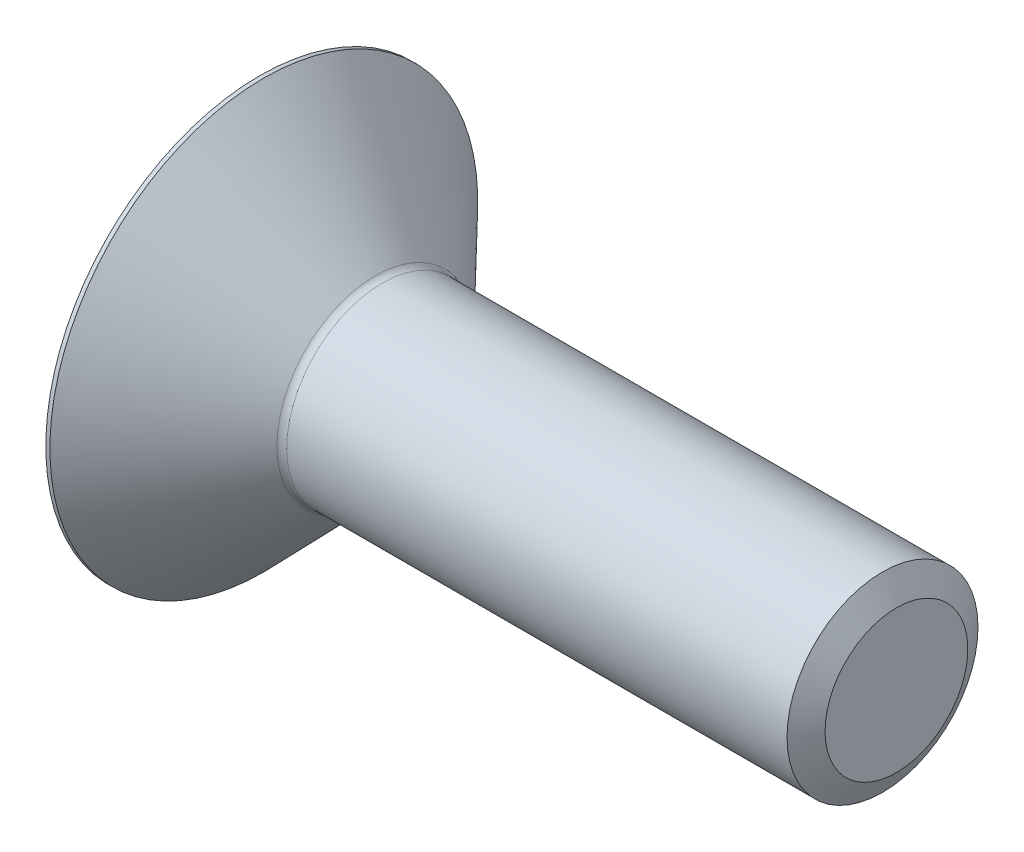
SolidWorks part; units mm, degrees
ref_plane "前视基准面" through (0, 0, 0) normal (0, 0, 1) x (1, 0, 0)
ref_plane "上视基准面" through (0, 0, 0) normal (0, 1, 0) x (1, 0, 0)
ref_plane "右视基准面" through (0, 0, 0) normal (1, 0, 0) x (0, 0, -1)
sketch "尺寸草图" plane through (0, 0, 0) normal (0, 0, 1) x (1, 0, 0)
  line L0 (0, 0) -> (40, 0) construction
  line L1 (40, 0) -> (40, 6) construction
  line L2 (40, 6) -> (38.25, 6) construction
  line L3 (38.25, 6) -> (8, 6) construction
  line L4 (0, 13.44) -> (7.44, 13.44) construction
  line L5 (7.44, 13.44) -> (8.04, 13.44) construction
  point P3 (40, 6.75)
  point P7 (0, 13.44)
  point P8 (0, 6)
  point P9 (0, 9.15)
  point P13 (0, 4)
  point P15 (4.3, 13.44)
  point P16 (6.24, 13.44)
  dimension "l" = 40
  dimension "d" = 12
  dimension "P" = 1.75
  dimension "b" = 32
  dimension "da" = 13.5
  dimension "dk" = 26.88
  dimension "ds" = 12
  dimension "e" = 9.15
  dimension "k" = 7.44
  dimension "r" = 0.6
  dimension "s" = 8
  dimension "t" = 4.3
  dimension "w" = 1.8
sketch "草图1" plane through (0, 0, 0) normal (0, 0, 1) x (1, 0, 0)
  line L0 (0, 6) -> (-32.3053, 6)
  line L1 (-32.7369, 6.1832) -> (-39.7447, 13.44)
  line L2 (-39.7447, 13.44) -> (-40, 13.44)
  line L3 (-40, 13.44) -> (-40, 0)
  line L4 (-40, 0) -> (0, 0)
  line L5 (0, 0) -> (0, 6)
  line L6 (0, 0) -> (-40, 0) construction
  arc A0 (-32.3053, 6) -> (-32.7369, 6.1832) centre (-32.3053, 6.6) cw
  point P9 (-32.56, 6)
  dimension "r" = 0.6
  dimension "k" = 7.44
  dimension "dk" = 26.88
  dimension "l" = 40
  dimension "D5" = 46
  dimension "d" = 12
revolve "旋转1" add sketch "草图1" angle 360 about L6
cosmetic thread "装饰螺纹线1" parameters "b"=32, "D2"=9.6
sketch "草图2" plane through (-40, 0, 0) normal (-1, 0, 0) x (0, 0, 1)
  line L0 (0, 0) -> (0, 6) construction
  line L1 (0, 4.6188) -> (-4, 2.3094)
  line L2 (-4, 2.3094) -> (-4, -2.3094)
  line L3 (-4, -2.3094) -> (0, -4.6188)
  line L4 (0, -4.6188) -> (4, -2.3094)
  line L5 (4, -2.3094) -> (4, 2.3094)
  line L6 (4, 2.3094) -> (0, 4.6188)
  circle A0 centre (0, 0) radius 4 construction
  point P1 (0, 4.5312)
  dimension "s" = 8
  dimension "e" = 9.15
extrude "切除-拉伸1" cut sketch "草图2" against normal blind 7.44
sketch "草图6" plane through (0, 0, 0) normal (0, 0, 1) x (1, 0, 0)
  line L0 (-35.7, 4.6188) -> (-33.0333, 0)
  line L1 (-33.0333, 0) -> (-31.41, 0)
  line L2 (-31.41, 0) -> (-31.41, 4.6188)
  line L3 (-31.41, 4.6188) -> (-35.7, 4.6188)
  line L4 (-40, 0) -> (-32.56, 0) construction
  line L5 (-40, 0) -> (-49.15, 0) construction
  dimension "D1" = 60
  dimension "t" = 4.3
  dimension "t1" = 7.44
  dimension "e-s" = 1.15
  dimension "e" = 9.15
revolve "旋转2" add sketch "草图6" angle 360 about L4
sketch "草图7" plane through (0, 0, 0) normal (0, 0, 1) x (1, 0, 0)
  line L0 (-40, 4.6188) -> (-40, 0)
  line L1 (-40, 0) -> (-38.85, 0)
  line L2 (-38.85, 0) -> (-40, 4.6188)
  line L3 (-40, 0) -> (-38.85, 0) construction
  dimension "e-s*1.1" = 1.15
revolve "切除-旋转2" cut sketch "草图7" angle 360 about L3
sketch "草图4" plane through (0, 0, 0) normal (0, 0, 1) x (1, 0, 0)
  line L0 (-0.875, 6) -> (0, 4.4845)
  line L1 (0, -6) -> (0, 6) construction
  line L2 (0, 4.4845) -> (0.875, 6)
  line L3 (0.875, 6) -> (-0.875, 6)
  line L4 (-0.875, 0) -> (0.875, 0) construction
  dimension "d" = 12
  dimension "p" = 1.75
revolve "切除-旋转1" cut sketch "草图4" angle 360 about L4
ref_axis "基准轴1" through (-21.1715, 0, 0) along (1, 0, 0)
pattern_linear "阵列(线性)2" [suppressed] count 18 spacing 1.75 along (-1, 0, 0) of bodies 104
ref_plane "基准面1" through (-32.3053, 0, 0) normal (1, 0, 0) x (0, 0, -1)
